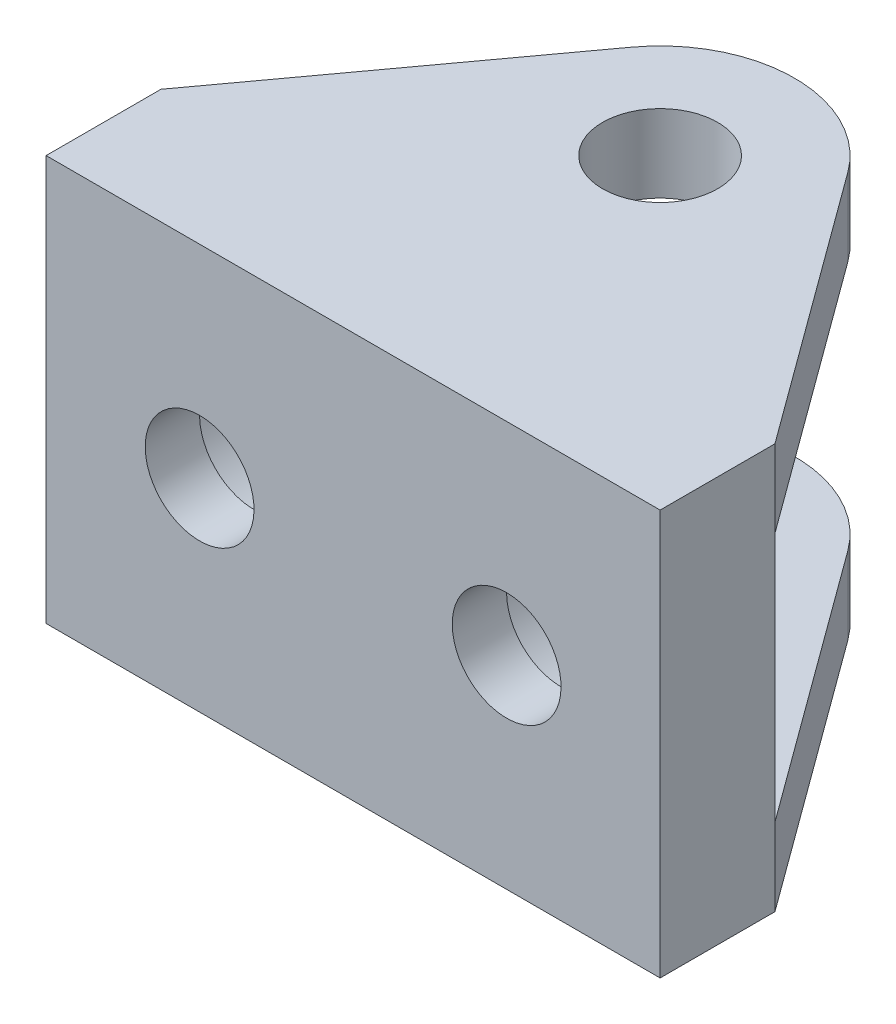
SolidWorks part; units mm, degrees
ref_plane "Front Plane" through (0, 0, 0) normal (0, 0, 1) x (1, 0, 0)
ref_plane "Top Plane" through (0, 0, 0) normal (0, 1, 0) x (1, 0, 0)
ref_plane "Right Plane" through (0, 0, 0) normal (1, 0, 0) x (0, 0, -1)
sketch "Sketch1" plane through (0, 0, 0) normal (0, 1, 0) x (1, 0, 0)
  line L0 (0, 0) -> (50.8, 0)
  line L1 (50.8, 0) -> (50.8, 9.4996)
  line L2 (0, 0) -> (0, 9.4996)
  line L3 (50.8, 9.4996) -> (34.3689, 31.961)
  line L4 (0, 9.4996) -> (16.4311, 31.961)
  line L5 (25.4, 0) -> (25.4, 43.8119) construction
  circle A0 centre (25.4, 25.4) radius 4.7625
  arc A1 (34.3689, 31.961) -> (16.4311, 31.961) centre (25.4, 25.4) ccw
  dimension "D4" = 6.35
  dimension "D5" = 9.525
  dimension "D1" = 25.4
  dimension "D2" = 50.8
  dimension "D3" = 9.4996
extrude "Boss-Extrude1" add sketch "Sketch1" along normal blind 33.528
sketch "Sketch2" plane through (50.8, 0, 0) normal (1, 0, 0) x (0, 0, -1)
  line L0 (9.4996, 16.764) -> (9.4996, 27.1145)
  line L1 (9.4996, 33.528) -> (9.4996, 0) construction
  line L2 (9.4996, 27.1145) -> (41.2496, 27.1145)
  line L3 (9.4996, 16.764) -> (9.4996, 6.4135)
  line L4 (9.4996, 6.4135) -> (41.2496, 6.4135)
  line L5 (41.2496, 6.4135) -> (41.2496, 27.1145)
  dimension "D1" = 20.701
  dimension "D2" = 31.75
extrude "Cut-Extrude1" cut sketch "Sketch2" against normal through all
sketch "Sketch3" plane through (0, 0, -9.4996) normal (0, 0, -1) x (-1, 0, 0)
  line L0 (-50.8, 16.764) -> (0, 16.764) construction
  line L1 (-50.8, 27.1145) -> (-50.8, 6.4135) construction
  line L2 (0, 27.1145) -> (0, 6.4135) construction
  line L3 (-25.4, 16.764) -> (-25.4, 27.1145) construction
  line L4 (0, 27.1145) -> (-50.8, 27.1145) construction
  point P10 (-38.1, 16.764)
  point P11 (-12.7, 16.764)
  dimension "D1" = 12.7
  dimension "D2" = 25.4
hole_wizard "CBORE for M8 Hex Head Bolt1" positions "Sketch3" profile "Sketch4" counterbore size "M8" standard "ANSI Metric" end condition through all
sketch "Sketch4" plane through (12.7, 16.764, -9.4996) normal (1, 0, 0) x (0, 1, 0)
  line L0 (0, 0) -> (0, 9.4996)
  line L1 (0, 9.4996) -> (4.5, 9.4996)
  line L3 (4.5, 9.4996) -> (4.5, 5)
  line L4 (4.5, 5) -> (8, 5)
  line L5 (8, 5) -> (8, 0)
  line L7 (8, 0) -> (0, 0)
  line L11 (0, -6.35) -> (0, 107.95) construction
  dimension "Thru Hole Dia." = 9
  dimension "Thru Hole Depth" = 9.4996
  dimension "C'Bore Dia." = 16
  dimension "C'Bore Depth" = 5
equation "\"1inch\"=62.1211"
